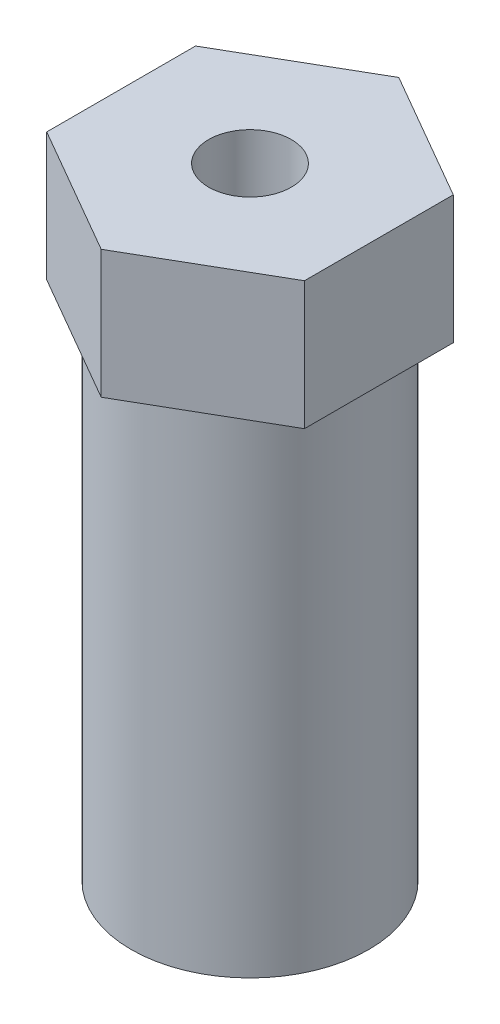
SolidWorks part; units mm, degrees
material "Brass"
ref_plane "Front" through (0, 0, 0) normal (0, 0, 1) x (1, 0, 0)
ref_plane "Top" through (0, 0, 0) normal (0, 1, 0) x (1, 0, 0)
ref_plane "Right" through (0, 0, 0) normal (1, 0, 0) x (0, 0, -1)
sketch "Sketch1" plane through (0, 0, 0) normal (0, 1, 0) x (1, 0, 0)
  circle A0 centre (0, 0) radius 5.75
  dimension "D1" = 11.5
extrude "cylinderBase" add sketch "Sketch1" along normal blind 30.07
sketch "Sketch2" plane through (0, 30.07, 0) normal (0, 1, 0) x (1, 0, 0)
  circle A2 centre (0, 0) radius 3.34
  circle A3 centre (0, 0) radius 3.34
  dimension "D1" = 2.41
extrude "throughHole" cut sketch "Sketch2" against normal through all
sketch "Sketch3" plane through (0, 30.07, 0) normal (0, 1, 0) x (1, 0, 0)
  line L1 (0, -7.2) -> (6.2354, -3.6)
  line L2 (6.2354, -3.6) -> (6.2354, 3.6)
  line L3 (6.2354, 3.6) -> (0, 7.2)
  line L4 (0, 7.2) -> (-6.2354, 3.6)
  line L5 (-6.2354, 3.6) -> (-6.2354, -3.6)
  line L6 (-6.2354, -3.6) -> (0, -7.2)
  circle A0 centre (0, 0) radius 6.2354 construction
  dimension "D1" = 7.2
extrude "Boss-Extrude2" add sketch "Sketch3" against normal blind 6.2
sketch "Sketch4" plane through (0, 30.07, 0) normal (0, 1, 0) x (1, 0, 0)
  circle A0 centre (0, 0) radius 2
  dimension "D1" = 4
extrude "Cut-Extrude2" cut sketch "Sketch4" against normal through all
